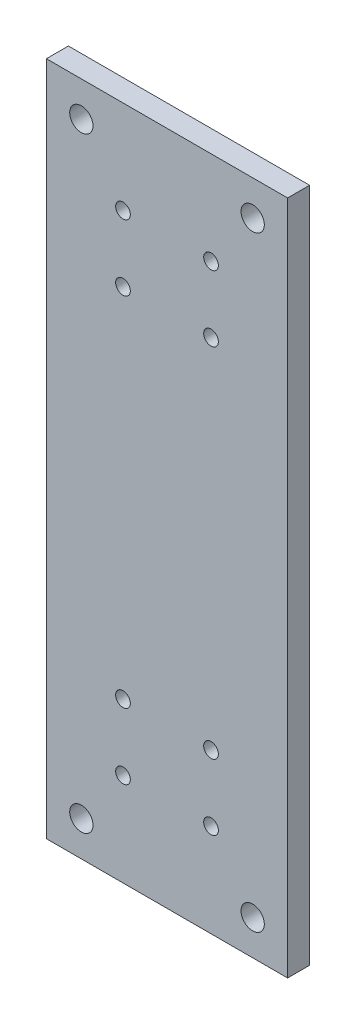
SolidWorks part; units mm, degrees
ref_plane "Front Plane" through (0, 0, 0) normal (0, 0, 1) x (1, 0, 0)
ref_plane "Top Plane" through (0, 0, 0) normal (0, 1, 0) x (1, 0, 0)
ref_plane "Right Plane" through (0, 0, 0) normal (1, 0, 0) x (0, 0, -1)
sketch "Sketch1" plane through (0, 0, 0) normal (0, 0, 1) x (1, 0, 0)
  line L0 (32.875, 184.15) -> (32.875, 0) construction
  line L1 (0, 0) -> (65.75, 0)
  line L2 (0, 0) -> (0, 184.15)
  line L3 (0, 184.15) -> (65.75, 184.15)
  line L4 (65.75, 0) -> (65.75, 184.15)
  circle A0 centre (9.525, 9.525) radius 3.175
  circle A1 centre (56.225, 9.525) radius 3.175
  circle A2 centre (56.225, 174.625) radius 3.175
  circle A3 centre (9.525, 174.625) radius 3.175
  circle A4 centre (20.875, 158.75) radius 2
  circle A5 centre (44.875, 158.75) radius 2
  circle A6 centre (44.875, 140.75) radius 2
  circle A7 centre (20.875, 140.75) radius 2
  circle A8 centre (20.875, 43.4) radius 2
  circle A9 centre (44.875, 43.4) radius 2
  circle A10 centre (44.875, 25.4) radius 2
  circle A11 centre (20.875, 25.4) radius 2
  dimension "D3" = 6.35
  dimension "D7" = 9.525
  dimension "D8" = 4
  dimension "D11" = 4
  dimension "D1" = 184.15
  dimension "D2" = 65.75
  dimension "D4" = 9.525
  dimension "D5" = 9.525
  dimension "D6" = 9.525
  dimension "D9" = 24
  dimension "D10" = 18
  dimension "D12" = 24
  dimension "D13" = 18
  dimension "D14" = 12
  dimension "D15" = 12
  dimension "D16" = 25.4
  dimension "D17" = 25.4
extrude "Boss-Extrude1" add sketch "Sketch1" along normal blind 5.9944
